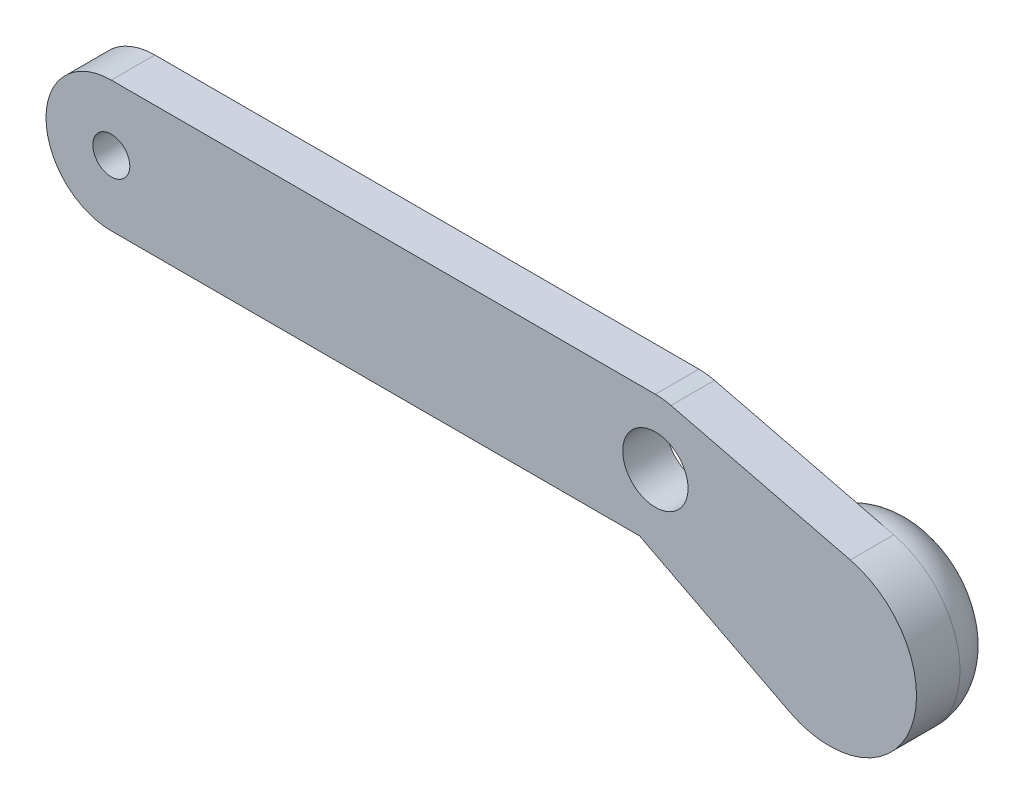
SolidWorks part; units mm, degrees
ref_plane "前视基准面" through (0, 0, 0) normal (0, 0, 1) x (1, 0, 0)
ref_plane "上视基准面" through (0, 0, 0) normal (0, 1, 0) x (1, 0, 0)
ref_plane "右视基准面" through (0, 0, 0) normal (1, 0, 0) x (0, 0, -1)
other "Configuration Table"
sketch "草图1" plane through (0, 0, 0) normal (0, 0, 1) x (1, 0, 0)
  line L0 (0, 0) -> (25, 0) construction
  line L1 (0, 3) -> (25, 3)
  line L2 (0, -3) -> (25, -3)
  arc A0 (0, 3) -> (0, -3) centre (0, 0) ccw
  arc A1 (25, -3) -> (25, 3) centre (25, 0) ccw
  circle A2 centre (0, 0) radius 1.5
  circle A3 centre (25, 0) radius 1.5
  point P3 (12.5, 0)
  dimension "D2" = 3
  dimension "D3" = 3
  dimension "D4" = 3
  dimension "D1" = 25
extrude "凸台-拉伸1" add sketch "草图1" along normal blind 2
sketch "草图4" plane through (0, 0, 0) normal (0, 0, -1) x (-1, 0, 0)
  circle A0 centre (0, 0) radius 1.5 construction
  circle A1 centre (0, 0) radius 1.5
  circle A2 centre (0, 0) radius 0.85
  circle M5 centre (0, 0) radius 1.5
  dimension "D1" = 1.7
extrude "凸台-拉伸6" add sketch "草图4" against normal through all contours A2 M5 region at (1.4576, 0, 0)
sketch "草图5" plane through (0, 0, 0) normal (0, 0, -1) x (-1, 0, 0)
  line L0 (-25.7174, 2.913) -> (-33.9565, 0.884)
  line L1 (-23.6251, -2.6664) -> (-31.1668, -6.5552)
  arc A0 (-25, 3) -> (-25, -3) centre (-25, 0) ccw construction
  arc A1 (-25, 3) -> (-25.7174, 2.913) centre (-25, 0) ccw
  arc A2 (-23.6251, -2.6664) -> (-25.7174, 2.913) centre (-25, 0) ccw
  arc A3 (-33.9565, 0.884) -> (-31.1668, -6.5552) centre (-33, -3) ccw
  arc M5 (-25, 3) -> (-25, -3) centre (-25, 0) ccw
  line M6 (-25, -3) -> (0, -3)
  dimension "D3" = 4
  dimension "D1" = 33
  dimension "D2" = 3
extrude "凸台-拉伸7" add sketch "草图5" against normal blind 2 contours L0 A3 L1 M6 M5 region at (31.6947, -2.5087, 0)
sketch "草图6" plane through (0, 0, 0) normal (0, 0, -1) x (-1, 0, 0)
  circle A0 centre (-33, -3) radius 4
extrude "凸台-拉伸8" add sketch "草图6" along normal blind 2
fillet "圆角1" radius 2 1 edges at (29, -3, -2)
